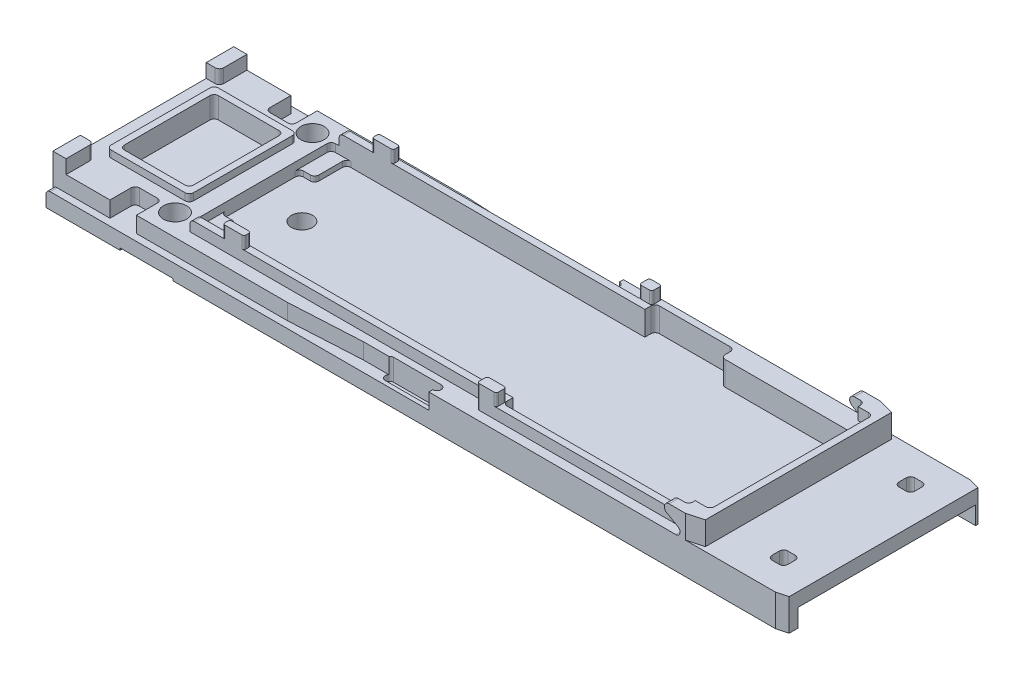
SolidWorks part; units mm, degrees
material "6063-T5"
ref_plane "Front Plane" through (0, 0, 0) normal (0, 0, 1) x (1, 0, 0)
ref_plane "Top Plane" through (0, 0, 0) normal (0, 1, 0) x (1, 0, 0)
ref_plane "Right Plane" through (0, 0, 0) normal (1, 0, 0) x (0, 0, -1)
sketch "Sketch1" plane through (0, 0, 0) normal (0, 1, 0) x (1, 0, 0)
  line L1 (-35, 9.2) -> (35, 9.2)
  line L2 (-35, 9.2) -> (-35, -9.2)
  line L3 (-35, -9.2) -> (35, -9.2)
  line L4 (35, 9.2) -> (35, -9.2)
  line L5 (-35, 9.2) -> (35, -9.2) construction
  line L6 (-35, -9.2) -> (35, 9.2) construction
  point P0 (0, 0)
  dimension "D1" = 70
  dimension "D2" = 18.4
extrude "Boss-Extrude1" add sketch "Sketch1" along normal blind 4.05
sketch "Sketch2" plane through (0, 4.05, 0) normal (0, 1, 0) x (1, 0, 0)
  line L0 (-35, 9.2) -> (-35, -9.2) construction
  line L1 (-23.95, 6.725) -> (-23.95, -6.725)
  line L2 (-23.95, -6.725) -> (6.7, -6.725)
  line L3 (6.7, -6.725) -> (6.7, -7.7)
  line L4 (6.7, -7.7) -> (26.3, -7.7)
  line L6 (26.3, -7.7) -> (26.3, 7.7)
  line L7 (26.3, 7.7) -> (5.7, 7.7)
  line L8 (5.7, 7.7) -> (5.7, 6.725)
  line L9 (5.7, 6.725) -> (-23.95, 6.725)
  line L10 (0, 0) -> (26.3, 0) construction
  dimension "D1" = 13.45
  dimension "D2" = 15.4
  dimension "D3" = 20.6
  dimension "D4" = 50.25
  dimension "D5" = 11.05
  dimension "D6" = 19.6
extrude "Cut-Extrude1" cut sketch "Sketch2" against normal blind 2.28
sketch "Sketch5" plane through (0, 4.05, 0) normal (0, 1, 0) x (1, 0, 0)
  line L0 (-23.95, 0) -> (-35, 0) construction
  line L1 (-32.75, 4.45) -> (-26.2, 4.45)
  line L2 (-32.75, 4.45) -> (-32.75, -4.45)
  line L3 (-32.75, -4.45) -> (-26.2, -4.45)
  line L4 (-26.2, 4.45) -> (-26.2, -4.45)
  line L5 (-32.75, 4.45) -> (-26.2, -4.45) construction
  line L6 (-32.75, -4.45) -> (-26.2, 4.45) construction
  line L7 (-23.95, 6.725) -> (-23.95, -6.725) construction
  line L8 (-35, 9.2) -> (-35, -9.2) construction
  point P0 (-29.475, 0)
  dimension "D1" = 8.9
  dimension "D2" = 6.55
extrude "Cut-Extrude2" cut sketch "Sketch5" against normal blind 2.38
sketch "Sketch17" plane through (0, 4.05, 0) normal (0, 1, 0) x (1, 0, 0)
  line L0 (-35, -9.2) -> (35, -9.2) construction
  line L1 (35, 9.2) -> (35, -9.2)
  line L2 (0, 0) -> (26.95, 0) construction
  line L4 (26.3, -7.7) -> (26.3, 7.7) construction
  line L5 (5.7, 7.7) -> (5.7, 6.725) construction
  line L11 (-35, 9.2) -> (35, 9.2)
  line L12 (-35, 9.2) -> (-35, -9.2)
  line L13 (-35, -9.2) -> (35, -9.2)
  line L14 (-23.2, 7.375) -> (-23.2, -7.375)
  line L57 (-23.2, -7.375) -> (5.05, -7.375)
  line L58 (5.05, -7.375) -> (5.05, -8.325)
  line L59 (5.05, -8.325) -> (26.95, -8.325)
  line L60 (26.95, -8.325) -> (26.95, 8.325)
  line L61 (26.95, 8.325) -> (5.05, 8.325)
  line L62 (5.05, 8.325) -> (5.05, 7.375)
  line L63 (5.05, 7.375) -> (-23.2, 7.375)
  dimension "D1" = 11.8
  dimension "D2" = 7.375
  dimension "D3" = 8.325
  dimension "D4" = 0.65
  dimension "D5" = 0.65
extrude "Cut-Extrude8" cut sketch "Sketch17" against normal blind 1.05
sketch "Sketch18" plane through (0, 0, 0) normal (0, 1, 0) x (1, 0, 0)
  line L10 (-32.75, 4.45) -> (-26.2, 4.45) construction
  line L11 (-26.2, -4.45) -> (-26.2, 4.45) construction
  line L12 (-32.75, -4.45) -> (-26.2, -4.45) construction
  line L13 (-32.75, 4.45) -> (-32.75, -4.45) construction
  line L14 (-33.375, 5.075) -> (-33.375, -5.075)
  line L15 (-33.375, -5.075) -> (-25.575, -5.075)
  line L16 (-25.575, -5.075) -> (-25.575, 5.075)
  line L17 (-25.575, 5.075) -> (-33.375, 5.075)
  line L18 (-33.375, 5.075) -> (-33.375, -5.075)
  line L19 (-33.375, -5.075) -> (-25.575, -5.075)
  line L20 (-25.575, -5.075) -> (-25.575, 5.075)
  line L21 (-25.575, 5.075) -> (-33.375, 5.075)
  line L22 (-32.75, 4.45) -> (-26.2, 4.45)
  line L23 (-26.2, -4.45) -> (-26.2, 4.45)
  line L24 (-32.75, -4.45) -> (-26.2, -4.45)
  line L25 (-32.75, 4.45) -> (-32.75, -4.45)
  dimension "D1" = 0.625
extrude "Boss-Extrude3" add sketch "Sketch18" along normal blind 3.67
hole_wizard "CSK for M2 Countersunk Flat Head Screw1" positions "Sketch7" profile "Sketch6" countersink size "M2" standard "ISO" end condition through all
sketch "Sketch7" plane through (-7.9019, 0, 3.8056) normal (0, 1, 0) x (-1, 0, 0)
  line L0 (-7.9019, -3.8056) -> (27.0981, -3.8056) construction
  line L1 (27.0981, -13.0056) -> (27.0981, 5.3944) construction
  line L4 (27.0981, 5.3944) -> (27.0981, -13.0056) construction
  point P0 (17.5981, -10.3056)
  point P1 (17.5981, 2.6944)
  dimension "D1" = 13
  dimension "D2" = 9.5
sketch "Sketch6" plane through (-25.5, 0, -6.5) normal (1, 0, 0) x (0, 0, -1)
  line L0 (0, 0) -> (0, 4.05)
  line L1 (0, 4.05) -> (1.1, 4.05)
  line L2 (1.1, 4.05) -> (1.1, 1.3)
  line L3 (1.1, 1.3) -> (2.2, 0.2)
  line L4 (2.2, 0.2) -> (2.2, 0)
  line L6 (2.2, 0) -> (0, 0)
  line L7 (-1.1, 1.3) -> (-2.2, 0.2) construction
  line L11 (0, -6.35) -> (0, 107.95) construction
  dimension "Thru Hole Dia." = 2.2
  dimension "Thru Hole Depth" = 4.05
  dimension "C'Sink Dia." = 4.4
  dimension "C'Sink Angle" = 90
  dimension "Head Clearance" = 0.2
sketch "Sketch13" plane through (0, 4.05, 0) normal (0, 1, 0) x (1, 0, 0)
  line L0 (-35, 9.2) -> (1.2, 9.2)
  line L1 (35, 9.2) -> (35, -9.2) construction
  line L2 (1.2, 9.2) -> (1.2, 8.175)
  line L3 (1.2, 8.175) -> (-6, 8.175)
  line L4 (-6, 8.175) -> (-12.8, 8.55)
  line L5 (-12.8, 8.55) -> (-35, 8.55)
  line L6 (-35, 8.55) -> (-35, 9.2)
  line L10 (35, 9.2) -> (-35, 9.2) construction
  line L11 (-35, 9.2) -> (-35, -9.2) construction
  dimension "D1" = 8.175
  dimension "D2" = 33.8
  dimension "D3" = 7.2
  dimension "D4" = 6.8
  dimension "D5" = 0.65
extrude "Cut-Extrude5" cut sketch "Sketch13" against normal offset from surface (2.55 mm away) 1.5 up to face at (-25.5, 0, -8.7)
sketch "Sketch19" plane through (0, 0, 0) normal (0, 1, 0) x (1, 0, 0)
  line L1 (-35, 8.55) -> (-33.75, 8.55)
  line L2 (-35, 8.55) -> (-35, 5.95)
  line L3 (-35, 5.95) -> (-33.75, 5.95)
  line L4 (-33.75, 8.55) -> (-33.75, 5.95)
  dimension "D1" = 2.6
  dimension "D2" = 1.25
extrude "Boss-Extrude4" add sketch "Sketch19" along normal blind 4.3
sketch "Sketch20" plane through (0, 3, 0) normal (0, 1, 0) x (1, 0, 0)
  line L0 (-33.75, 8.55) -> (-12.8, 8.55) construction
  line L1 (-29.6, 8.55) -> (-27.1, 8.55)
  line L2 (-29.6, 8.55) -> (-29.6, 6.165)
  line L3 (-29.6, 6.165) -> (-27.1, 6.165)
  line L4 (-27.1, 8.55) -> (-27.1, 6.165)
  line L5 (-35, -9.2) -> (-35, 5.95) construction
  dimension "D1" = 2.5
  dimension "D2" = 6.165
  dimension "D3" = 5.4
extrude "Cut-Extrude9" cut sketch "Sketch20" against normal up to surface (1.5 mm away) up to face at (-14.4, 1.5, -8.6417)
sketch "Sketch21" plane through (0, 0, 0) normal (0, 1, 0) x (1, 0, 0)
  line L0 (5.05, 7.375) -> (-23.2, 7.375) construction
  line L1 (-20.1, 7.375) -> (-18.1, 7.375)
  line L2 (-20.1, 7.375) -> (-20.1, 6.725)
  line L3 (-20.1, 6.725) -> (-18.1, 6.725)
  line L4 (-18.1, 7.375) -> (-18.1, 6.725)
  line L5 (5.7, 6.725) -> (-23.95, 6.725) construction
  line L6 (-23.2, 7.375) -> (-23.2, 6.725) construction
  dimension "D1" = 2
  dimension "D2" = 5.1
extrude "Boss-Extrude5" add sketch "Sketch21" along normal blind 5.2
sketch "Sketch22" plane through (0, 0, 0) normal (0, -1, 0) x (1, 0, 0)
  line L0 (24.9, -7.7) -> (26.95, -7.7)
  line L1 (26.3, -7.7) -> (5.7, -7.7) construction
  line L2 (26.95, -8.325) -> (26.95, 8.325) construction
  line L3 (26.95, -7.7) -> (26.95, -9.2)
  line L4 (1.2, -9.2) -> (35, -9.2) construction
  line L5 (26.95, -9.2) -> (22.15, -9.2)
  line L6 (22.15, -9.2) -> (22.15, -8.325)
  line L7 (5.05, -8.325) -> (26.95, -8.325) construction
  line L8 (22.15, -8.325) -> (24.9, -8.325)
  line L9 (24.9, -8.325) -> (24.9, -7.7)
  dimension "D1" = 4.8
  dimension "D2" = 2.05
extrude "Boss-Extrude6" add sketch "Sketch22" against normal blind 5.2
chamfer "Chamfer2" distance 1.5 angle 15 1 edges at (26.95, 4.1, -9.2)
chamfer "Chamfer1" distance 1 angle 15 2 edges at (35, 1.5, -9.2) (35, 1.5, 9.2)
sketch "Sketch25" plane through (0, 3, 0) normal (0, 1, 0) x (1, 0, 0)
  line L1 (31.2, 6.75) -> (31.9, 6.75)
  line L2 (30.8, 6.35) -> (30.8, 5.65)
  line L3 (31.2, 5.25) -> (31.9, 5.25)
  line L4 (32.3, 6.35) -> (32.3, 5.65)
  line L5 (30.8, 6.75) -> (32.3, 5.25) construction
  line L6 (30.8, 5.25) -> (32.3, 6.75) construction
  line L7 (35, -8.9321) -> (35, 8.9321) construction
  arc A0 (31.9, 6.75) -> (32.3, 6.35) centre (31.9, 6.35) cw
  arc A1 (32.3, 5.65) -> (31.9, 5.25) centre (31.9, 5.65) cw
  arc A2 (31.2, 5.25) -> (30.8, 5.65) centre (31.2, 5.65) cw
  arc A3 (30.8, 6.35) -> (31.2, 6.75) centre (31.2, 6.35) cw
  point P0 (31.55, 6)
  dimension "D5" = 0.4
  dimension "D1" = 1.5
  dimension "D2" = 1.5
  dimension "D3" = 6
  dimension "D4" = 4.2
extrude "Cut-Extrude10" cut sketch "Sketch25" against normal through all
sketch "Sketch16" plane through (0, 0, 0) normal (0, -1, 0) x (1, 0, 0)
  line L0 (-28, -9.2) -> (-28, -6.5)
  line L2 (-23, -6.5) -> (-23, -9.2)
  line L3 (-23, -9.2) -> (-28, -9.2)
  line L4 (34, -9.2) -> (-35, -9.2) construction
  arc A0 (-28, -6.5) -> (-23, -6.5) centre (-25.5, -6.5) cw
  circle A1 centre (-25.5, -6.5) radius 2.2 construction
  dimension "D1" = 5
extrude "Cut-Extrude7" cut sketch "Sketch16" against normal blind 0.2
mirror "Mirror1" about plane through (0, 0, 0) normal (0, 0, 1) of "Cut-Extrude10", "Boss-Extrude5", "Cut-Extrude9", "Boss-Extrude4", "Cut-Extrude5", "Cut-Extrude7", "Boss-Extrude6", "Chamfer2"
sketch "Sketch29" plane through (0, 0, -9.2) normal (0, 0, 1) x (1, 0, 0)
  line L0 (23.6939, 4.3603) -> (24.7572, 3.7464)
  line L1 (24.6572, 3.7464) -> (23.6689, 4.317) construction
  line L2 (24.5572, 3) -> (21.5572, 3)
  line L3 (34, 3) -> (25.45, 3) construction
  line L5 (22.15, 5.2) -> (25.45, 5.2) construction
  line L6 (23.9189, 5.2) -> (21.5572, 5.2)
  line L7 (21.5572, 5.2) -> (21.5572, 3)
  arc A0 (24.7572, 3.7464) -> (24.5572, 3) centre (24.5572, 3.4) cw
  arc A1 (23.6939, 4.3603) -> (23.9189, 5.2) centre (23.9189, 4.75) cw
  arc A2 (23.9189, 5.25) -> (23.6689, 4.317) centre (23.9189, 4.75) ccw construction
  dimension "D2" = 3
  dimension "D1" = 0.4
extrude "Cut-Extrude12" cut sketch "Sketch29" along normal up to surface (0.875 mm away) up to face at (23.525, 4.625, -8.325)
sketch "Sketch30" plane through (0, 0, 9.2) normal (0, 0, 1) x (1, 0, 0)
  line L0 (23.6939, 4.3603) -> (24.7572, 3.7464)
  line L1 (24.5572, 3) -> (21.5572, 3)
  line L2 (22.15, 5.2) -> (25.45, 5.2) construction
  line L3 (23.9189, 5.2) -> (21.5572, 5.2)
  line L4 (21.5572, 5.2) -> (21.5572, 3)
  line L6 (1.2, 3) -> (22.15, 3) construction
  line L7 (24.7572, 3.7464) -> (24.2313, 4.05) construction
  arc A0 (24.7572, 3.7464) -> (24.5572, 3) centre (24.5572, 3.4) cw
  arc A1 (23.9189, 5.2) -> (23.6939, 4.3603) centre (23.9189, 4.75) ccw construction
  arc A2 (23.6939, 4.3603) -> (23.9189, 5.2) centre (23.9189, 4.75) cw
  dimension "D1" = 3
  dimension "D3" = 0.4
extrude "Cut-Extrude13" cut sketch "Sketch30" against normal up to surface (0.875 mm away) up to face at (23.525, 4.625, 8.325)
sketch "Sketch26" plane through (0, 0, 0) normal (0, -1, 0) x (1, 0, 0)
  line L0 (5.05, 7.375) -> (-23.2, 7.375) construction
  line L1 (6.7, 8.325) -> (4.9, 8.325)
  line L2 (6.7, 8.325) -> (6.7, 7.375)
  line L3 (6.7, 7.375) -> (4.9, 7.375)
  line L4 (4.9, 8.325) -> (4.9, 7.375)
  line L5 (5.05, -7.375) -> (-18.1, -7.375) construction
  line L6 (5.7, -8.325) -> (4.52, -8.325)
  line L7 (5.7, -8.325) -> (5.7, -7.375)
  line L8 (5.7, -7.375) -> (4.52, -7.375)
  line L9 (4.52, -8.325) -> (4.52, -7.375)
  line L10 (6.7, 6.725) -> (6.7, 7.7) construction
  line L12 (24.5572, 8.325) -> (5.05, 8.325) construction
  line L13 (5.7, -7.7) -> (5.7, -6.725) construction
  line L14 (5.05, -8.325) -> (24.5572, -8.325) construction
  dimension "D1" = 1.8
  dimension "D2" = 1.18
extrude "Boss-Extrude8" add sketch "Sketch26" against normal blind 5.2
fillet "Fillet1" radius 0.4 2 edges at (-23.2, 4.05, 7.05) (-23.2, 4.05, -7.05)
fillet "Fillet2" radius 0.2 16 edges at (-18.1, 4.625, -6.725) (-20.1, 4.625, -6.725) (-20.1, 4.625, -7.375) (-18.1, 4.625, -7.375) (-18.1, 4.625, 6.725) (-18.1, 4.625, 7.375) (-20.1, 4.625, 6.725) (-20.1, 4.625, 7.375) (5.7, 4.625, -7.375) (4.52, 4.625, -7.375) (5.7, 4.625, -8.325) (4.52, 4.1, -8.325) (6.7, 4.625, 8.325) (4.9, 4.1, 8.325) (4.9, 4.625, 7.375) (6.7, 4.625, 7.375)
sketch "Sketch23" plane through (0, 4.05, 0) normal (0, 1, 0) x (1, 0, 0)
  line L4 (26.3, 7.7) -> (26.3, -7.7)
  line L5 (26.3, -7.7) -> (26.95, -7.7)
  line L6 (26.95, -7.7) -> (26.95, 7.7)
  line L7 (26.95, 7.7) -> (26.3, 7.7)
  line L8 (26.3, 7.7) -> (26.3, -7.7)
  line L9 (26.3, -7.7) -> (26.95, -7.7)
  line L10 (26.95, -7.7) -> (26.95, 7.7)
  line L11 (26.95, 7.7) -> (26.3, 7.7)
  dimension "D1" = 0
extrude "Boss-Extrude7" add sketch "Sketch23" along normal up to surface (1.15 mm away) up to face at (25.284, 5.2, -8.464)
sketch "Sketch27" plane through (0, 1.77, 0) normal (0, 1, 0) x (1, 0, 0)
  line L0 (26.3, 7.7) -> (5.7, 7.7) construction
  line L1 (13.2, 7.7) -> (26.3, 7.7)
  line L2 (13.2, 7.7) -> (13.2, 6.425)
  line L3 (13.2, 6.425) -> (26.3, 6.425)
  line L4 (26.3, 7.7) -> (26.3, 6.425)
  line L5 (26.3, -7.7) -> (26.3, 7.7) construction
  line L6 (24.2313, 8.325) -> (5.5, 8.325) construction
  line L7 (5.7, 7.7) -> (5.7, 6.725) construction
  dimension "D1" = 1.9
  dimension "D2" = 7.5
extrude "Boss-Extrude9" add sketch "Sketch27" along normal up to surface (2.28 mm away) up to face at (-4.2057, 4.05, -7.2117)
fillet "Fillet3" radius 0.4 2 edges at (13.2, 2.91, -7.7) (13.2, 2.91, -6.425)
sketch "Sketch28" plane through (0, 0, 0) normal (0, -1, 0) x (1, 0, 0)
  line L1 (35, 8.1) -> (30.8, 8.1)
  line L2 (35, 8.1) -> (35, -8.7)
  line L3 (35, 0) -> (0, 0) construction
  line L4 (30.8, 8.1) -> (30.8, -7)
  line L5 (30.8, 6.35) -> (30.8, 5.65) construction
  line L6 (35, -8.7) -> (14.2, -8.7)
  line L8 (30.8, -7) -> (14.2, -7)
  line L9 (14.2, -8.7) -> (14.2, -7)
  line L10 (34, -9.2) -> (-23, -9.2) construction
  line L11 (35, 8.9321) -> (35, -8.9321) construction
  line L12 (-23, 9.2) -> (34, 9.2) construction
  dimension "D1" = 2.2
  dimension "D2" = 0.5
  dimension "D3" = 1.1
  dimension "D4" = 16.6
extrude "Cut-Extrude11" cut sketch "Sketch28" against normal blind 1.7
sketch "Sketch31" plane through (0, 1.77, 0) normal (0, 1, 0) x (1, 0, 0)
  line L1 (-23.95, 6.725) -> (-22.5, 6.725)
  line L2 (-23.95, 6.725) -> (-23.95, 3.7)
  line L3 (-23.95, 3.7) -> (-22.5, 3.7)
  line L4 (-22.5, 6.725) -> (-22.5, 3.7)
  line L5 (-23.95, -6.725) -> (-22.5, -6.725)
  line L6 (-23.95, -6.725) -> (-23.95, -3.7)
  line L7 (-23.95, -3.7) -> (-22.5, -3.7)
  line L8 (-22.5, -6.725) -> (-22.5, -3.7)
  dimension "D1" = 7.4
  dimension "D2" = 1.45
extrude "Boss-Extrude10" add sketch "Sketch31" along normal blind 0.5
sketch "Sketch32" plane through (0, 1.5, 0) normal (0, 1, 0) x (1, 0, 0)
  line L1 (1.2, 8.175) -> (-3.3, 8.175)
  line L2 (1.2, 8.175) -> (1.2, 8.825)
  line L3 (1.2, 8.825) -> (-3.3, 8.825)
  line L4 (-3.3, 8.175) -> (-3.3, 8.825)
  line L5 (1.2, -8.175) -> (-3.3, -8.175)
  line L6 (1.2, -8.175) -> (1.2, -8.825)
  line L7 (1.2, -8.825) -> (-3.3, -8.825)
  line L8 (-3.3, -8.175) -> (-3.3, -8.825)
  dimension "D1" = 4.5
  dimension "D2" = 0.65
extrude "Cut-Extrude14" cut sketch "Sketch32" against normal blind 0.55
sketch "Sketch33" plane through (0, 0.95, 0) normal (0, 1, 0) x (1, 0, 0)
  line L1 (-3.3, -8.825) -> (1.2, -8.825)
  line L2 (1.2, -8.175) -> (1.2, -9.2) construction
  line L3 (-3.3, -8.025) -> (1.2, -8.025)
  arc A0 (-3.3, -8.025) -> (-3.3, -8.825) centre (-3.3, -8.425) ccw
  arc A1 (1.2, -8.025) -> (1.2, -8.825) centre (1.2, -8.425) cw
  dimension "D1" = 0.8
extrude "Cut-Extrude15" cut sketch "Sketch33" along normal through all
mirror "Mirror2" about plane through (0, 0, 0) normal (0, 0, 1) of "Cut-Extrude15"
fillet "Fillet5" radius 0.4 24 edges at (5.7, 2.91, -7.7) (26.3, 3.485, 7.7) (6.7, 2.91, 7.7) (-29.6, 2.25, -6.165) (-27.1, 2.25, -6.165) (24.9, 4.625, -8.325) (-27.1, 2.25, 6.165) (-29.6, 2.25, 6.165) (-26.2, 2.67, -4.45) (-26.2, 2.67, 4.45) (-32.75, 2.67, 4.45) (-32.75, 2.67, -4.45) (24.9, 4.625, 8.325) (26.3, 4.625, -7.7) (26.3, 2.91, -6.425) (14.2, 0.85, -8.7) (14.2, 0.85, -7) (30.8, 0.85, 8.1) (-23.95, 2.635, -6.725) (-23.95, 2.02, -3.7) (-22.5, 2.02, -6.725) (-23.95, 2.635, 6.725) (-23.95, 2.02, 3.7) (-22.5, 2.02, 6.725)
fillet "Fillet6" radius 0.4 2 edges at (-22.5, 2.02, -3.7) (-22.5, 2.02, 3.7)
fillet "Fillet7" radius 0.4 2 edges at (-35, 1.5, 8.875) (-35, 1.5, -8.875)
fillet "Fillet8" radius 0.4 6 edges at (-33.75, 3.65, -5.95) (-33.75, 3.65, 5.95) (-33.375, 3.335, -5.075) (-25.575, 3.335, -5.075) (-33.375, 3.335, 5.075) (-25.575, 3.335, 5.075)
sketch "Sketch34" plane through (0, 1.77, 0) normal (0, 1, 0) x (1, 0, 0)
  circle A0 centre (-20, 0) radius 1
  dimension "D1" = 2
  dimension "D2" = 20
extrude "Cut-Extrude16" cut sketch "Sketch34" against normal through all
